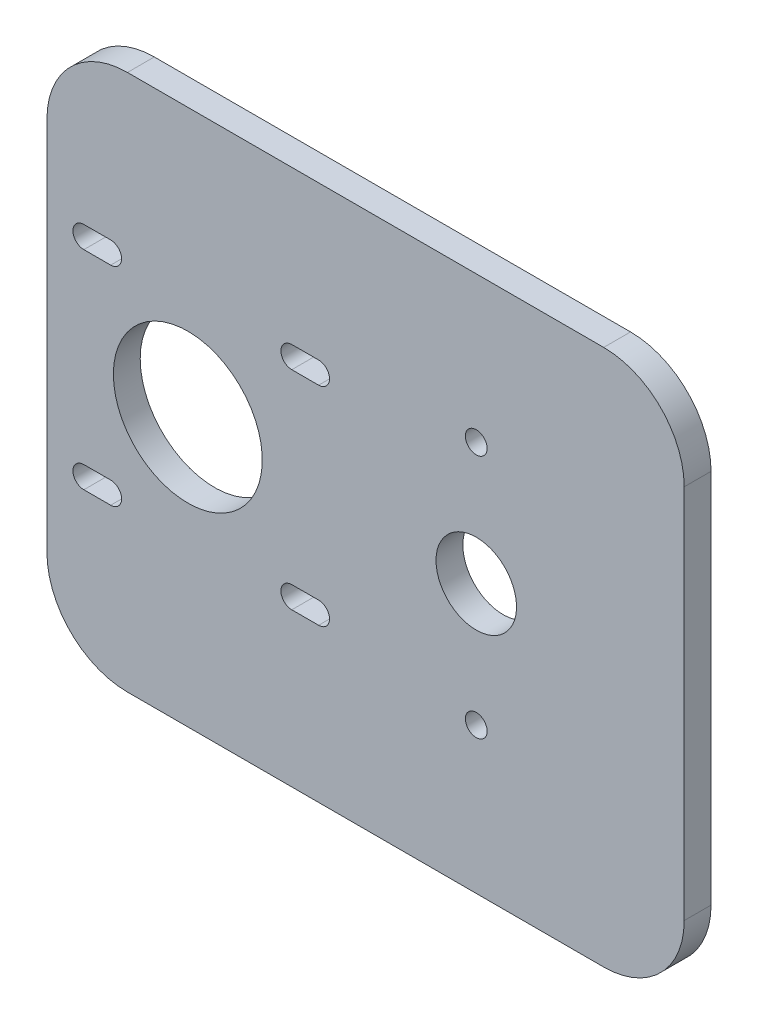
SolidWorks part; units mm, degrees
ref_plane "Alzado" through (0, 0, 0) normal (0, 0, 1) x (1, 0, 0)
ref_plane "Planta" through (0, 0, 0) normal (0, 1, 0) x (1, 0, 0)
ref_plane "Vista lateral" through (0, 0, 0) normal (1, 0, 0) x (0, 0, -1)
sketch "Croquis1" plane through (0, 0, 0) normal (0, 0, 1) x (1, 0, 0)
  line L1 (0, 0) -> (95, 0)
  line L2 (0, 0) -> (0, 80)
  line L3 (0, 80) -> (95, 80)
  line L4 (95, 0) -> (95, 80)
  dimension "D1" = 80
  dimension "D2" = 95
extrude "Saliente-Extruir1" add sketch "Croquis1" along normal blind 4
sketch "Croquis2" plane through (0, 0, 0) normal (0, 0, -1) x (-1, 0, 0)
  line L0 (0, 80) -> (0, 0) construction
  line L1 (-36.5, 55.5) -> (-40.5, 55.5) construction
  line L2 (-36.5, 53.875) -> (-40.5, 53.875)
  line L3 (-36.5, 57.125) -> (-40.5, 57.125)
  line L4 (-36.5, 24.5) -> (-40.5, 24.5) construction
  line L5 (-36.5, 22.875) -> (-40.5, 22.875)
  line L6 (-36.5, 26.125) -> (-40.5, 26.125)
  line L7 (-5.5, 24.5) -> (-9.5, 24.5) construction
  line L8 (-5.5, 22.875) -> (-9.5, 22.875)
  line L9 (-5.5, 26.125) -> (-9.5, 26.125)
  line L10 (-5.5, 55.5) -> (-9.5, 55.5) construction
  line L11 (-5.5, 53.875) -> (-9.5, 53.875)
  line L12 (-5.5, 57.125) -> (-9.5, 57.125)
  circle A3 centre (-21, 40) radius 11.1
  circle A5 centre (-64, 40) radius 6
  arc A7 (-36.5, 53.875) -> (-36.5, 57.125) centre (-36.5, 55.5) ccw
  arc A8 (-40.5, 57.125) -> (-40.5, 53.875) centre (-40.5, 55.5) ccw
  arc A9 (-36.5, 22.875) -> (-36.5, 26.125) centre (-36.5, 24.5) ccw
  arc A10 (-40.5, 26.125) -> (-40.5, 22.875) centre (-40.5, 24.5) ccw
  arc A11 (-5.5, 22.875) -> (-5.5, 26.125) centre (-5.5, 24.5) ccw
  arc A12 (-9.5, 26.125) -> (-9.5, 22.875) centre (-9.5, 24.5) ccw
  arc A13 (-5.5, 53.875) -> (-5.5, 57.125) centre (-5.5, 55.5) ccw
  arc A14 (-9.5, 57.125) -> (-9.5, 53.875) centre (-9.5, 55.5) ccw
  circle A15 centre (-64, 21.75) radius 1.625
  circle A16 centre (-64, 58.25) radius 1.625
  point P4 (-38.5, 55.5)
  point P17 (-38.5, 24.5)
  point P27 (-7.5, 24.5)
  point P34 (-7.5, 55.5)
  dimension "D1" = 3.25
  dimension "D2" = 4
  dimension "D3" = 3.25
  dimension "D4" = 4
  dimension "D5" = 22.2
  dimension "D6" = 12
  dimension "D13" = 3.25
  dimension "D14" = 3.25
  dimension "D7" = 3.25
  dimension "D8" = 4
  dimension "D9" = 3.25
  dimension "D10" = 4
  dimension "D11" = 64
  dimension "D12" = 40
  dimension "D15" = 18.25
  dimension "D16" = 18.25
extrude "Cortar-Extruir1" cut sketch "Croquis2" against normal through all
fillet "Redondeo1" radius 12 4 edges at (95, 0, 2) (95, 80, 2) (0, 0, 2) (0, 80, 2)
